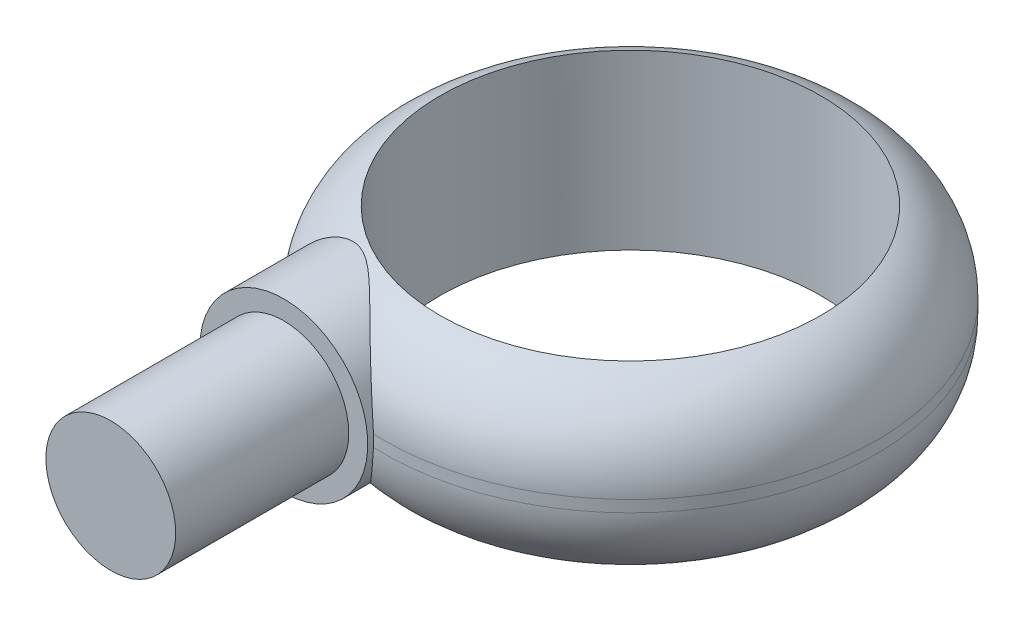
SolidWorks part; units mm, degrees
ref_plane "Front Plane" through (0, 0, 0) normal (0, 0, 1) x (1, 0, 0)
ref_plane "Top Plane" through (0, 0, 0) normal (0, 1, 0) x (1, 0, 0)
ref_plane "Right Plane" through (0, 0, 0) normal (1, 0, 0) x (0, 0, -1)
sketch "Sketch1" plane through (0, 0, 0) normal (0, 0, 1) x (1, 0, 0)
  circle A0 centre (0, 0) radius 6.1595 construction
  circle A1 centre (0, 0) radius 4.7625
  dimension "D1" = 12.319
  dimension "D2" = 9.525
extrude "Boss-Extrude1" add sketch "Sketch1" along normal blind 12.7
sketch "Sketch2" plane through (0, 0, 0) normal (0, 0, -1) x (-1, 0, 0)
  circle A0 centre (0, 0) radius 6.1595
extrude "Boss-Extrude2" add sketch "Sketch2" along normal blind 6.35
sketch "Sketch3" plane through (0, 0, 0) normal (0, 1, 0) x (1, 0, 0)
  line L0 (0, 6.35) -> (6.985, 18.4484) construction
  line L1 (6.1595, 6.35) -> (-6.1595, 6.35) construction
  circle A0 centre (6.985, 18.4484) radius 13.97
  circle A3 centre (6.985, 18.4484) radius 18.034
  dimension "D3" = 4.064
  dimension "D1" = 120
  dimension "D2" = 13.97
extrude "Boss-Extrude3" add sketch "Sketch3" along normal blind 6.35 and the other way blind 6.35
sketch "Sketch4" plane through (0, 6.35, 0) normal (0, 1, 0) x (1, 0, 0)
  circle A0 centre (6.985, 18.4484) radius 13.97
  circle A1 centre (6.985, 18.4484) radius 13.97 construction
extrude "Cut-Extrude1" cut sketch "Sketch4" against normal through all
fillet "Fillet1" radius 6.35 2 edges at (6.985, -6.35, -0.4144) (6.985, 6.35, -0.4144)
